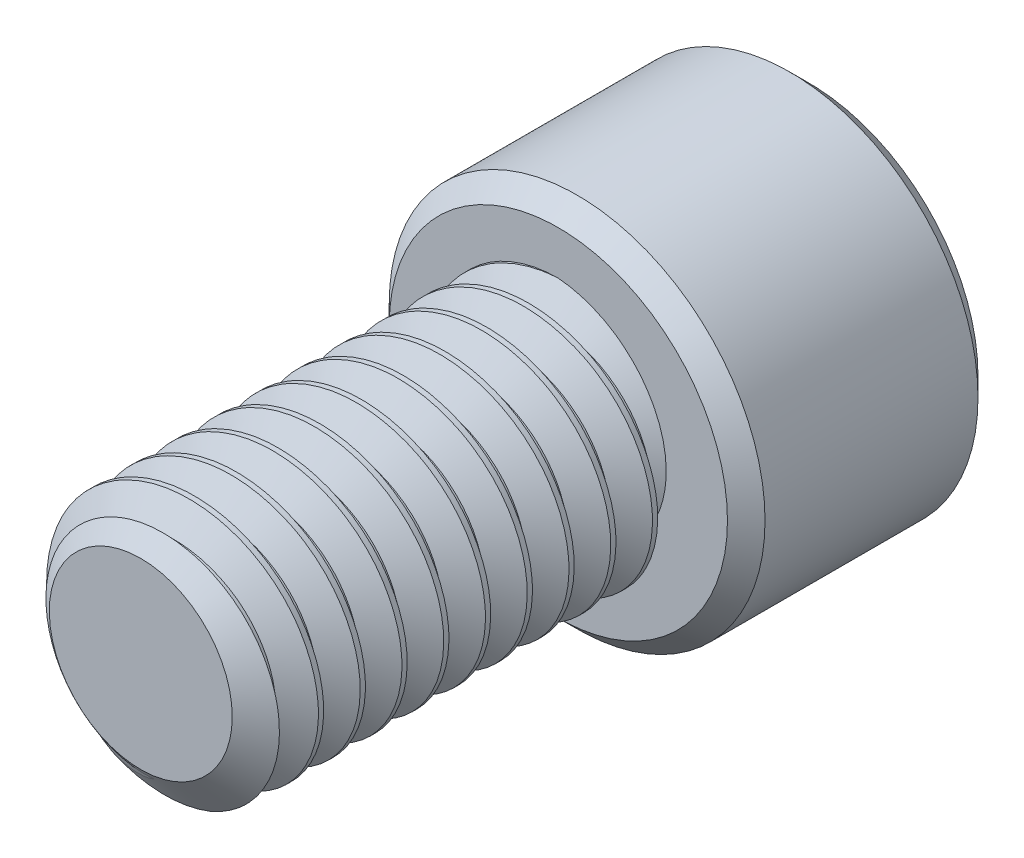
SolidWorks part; units mm, degrees
ref_plane "Front Plane" through (0, 0, 0) normal (0, 0, 1) x (1, 0, 0)
ref_plane "Top Plane" through (0, 0, 0) normal (0, 1, 0) x (1, 0, 0)
ref_plane "Right Plane" through (0, 0, 0) normal (1, 0, 0) x (0, 0, -1)
sketch "Sketch1" plane through (0, 0, 0) normal (0, 0, 1) x (1, 0, 0)
  circle A0 centre (0, 0) radius 4.7625
  dimension "OD" = 9.525
extrude "Extrude1" add sketch "Sketch1" against normal blind 15.875
sketch "Sketch2" plane through (0, 0, 0) normal (0, 0, 1) x (1, 0, 0)
  circle A0 centre (0, 0) radius 4.7625 construction
  circle A1 centre (0, 0) radius 4.7625
curve "Helix/Spiral1" pitch 1.5875 height 17.4625 turns 11 parameters "pitch"=1.5875
sketch "Sketch3" plane through (0, 0, 0) normal (1, 0, 0) x (0, 0, -1)
  line L0 (-1.3891, 4.7625) -> (-0.7938, 3.7314)
  line L1 (-0.7938, 3.7314) -> (-0.5953, 3.7314)
  line L2 (-0.5953, 3.7314) -> (0, 4.7625)
  line L3 (-1.3891, 4.7625) -> (0, 4.7625)
  line L4 (-0.6945, 4.7625) -> (-0.6945, 3.7314) construction
  line L5 (-1.0914, 4.2469) -> (-0.2977, 4.2469) construction
  line L6 (0, 4.7625) -> (0, -4.7625) construction
  dimension "D1" = 0.1984
  dimension "D2" = 0.7937
  dimension "D3" = 60
sweep "Cut-Sweep1" cut profiles "Sketch3" path "Helix/Spiral1"
sketch "Sketch4" plane through (0, 0, 0) normal (1, 0, 0) x (0, 0, -1)
  line L0 (0.8998, 4.7625) -> (0, 3.4774)
  line L1 (0, 3.4774) -> (0, 4.7625)
  line L2 (0.8998, 4.7625) -> (0, 4.7625)
  line L3 (-1.3891, 4.7625) -> (0, 4.7625) construction
  line L4 (0, 0) -> (7.0209, 0) construction
  dimension "D1" = 55
  dimension "D2" = 0.254
revolve "Cut-Revolve1" cut sketch "Sketch4" angle 360 about L4
sketch "Sketch5" plane through (0, 0, 0) normal (1, 0, 0) x (0, 0, -1)
  line L0 (15.875, -3.7535) -> (15.875, 3.3982) construction
  line L1 (15.875, 4.8895) -> (87.4665, 4.8895)
  line L2 (15.875, 4.8895) -> (15.875, 0)
  line L3 (15.875, 0) -> (87.3125, 0)
  line L4 (87.3125, 4.5593) -> (87.3125, 0)
  line L5 (87.4665, 4.8895) -> (87.3125, 4.5593)
  line L6 (0, 0) -> (9.9695, 0) construction
  point P3 (87.3125, 4.8895)
  point P10 (87.3125, 4.8895)
  dimension "D1" = 0.3302
  dimension "Thread min" = 87.3125
  dimension "D2" = 0.127
  dimension "D3" = 25
revolve "partially thread" add sketch "Sketch5" angle 360 about L6
sketch "Sketch6" plane through (0, 0, -15.875) normal (0, 0, -1) x (-1, 0, 0)
  circle A0 centre (0, 0) radius 7.1438
  dimension "head dia" = 14.2875
extrude "Extrude2" add sketch "Sketch6" along normal blind 9.525
sketch "Sketch7" plane through (0, 0, -25.4) normal (0, 0, -1) x (-1, 0, 0)
  line L1 (0, 4.5827) -> (-3.9688, 2.2914)
  line L2 (-3.9688, 2.2914) -> (-3.9688, -2.2914)
  line L3 (-3.9688, -2.2914) -> (0, -4.5827)
  line L4 (0, -4.5827) -> (3.9688, -2.2914)
  line L5 (3.9688, -2.2914) -> (3.9688, 2.2914)
  line L6 (3.9688, 2.2914) -> (0, 4.5827)
  circle A0 centre (0, 0) radius 3.9688 construction
  dimension "hex dia" = 7.9375
extrude "Cut-Extrude1" cut sketch "Sketch7" against normal blind 5.9531
sketch "Sketch8" plane through (0, 0, -25.4) normal (0, 0, -1) x (-1, 0, 0)
  circle A0 centre (0, 0) radius 4.5827
extrude "Cut-Extrude2" cut sketch "Sketch8" against normal through all draft 45
chamfer "Chamfer1" distance 0.7144 angle 45 2 edges at (-7.1438, 0, -25.4) (-7.1438, 0, -15.875)
sketch "Sketch9" plane through (0, 0, 0) normal (1, 0, 0) x (0, 0, -1)
  line L0 (0, 4.7625) -> (0, -4.7625) construction
  line L1 (8.7312, 4.7625) -> (8.7312, -4.7625) construction
  dimension "D1" = 8.7312
  dimension "D4" = 0.635
  dimension "D5" = 0.3302
equation "\"D3@Helix/Spiral1\" = \"screw length@Extrude1\"+\"pitch@Helix/Spiral1\""
equation "\"D1@Sketch3\" = \"pitch@Helix/Spiral1\"*.125"
equation "\"D2@Sketch3\" = \"pitch@Helix/Spiral1\"*.5"
equation "\"D1@Cut-Extrude1\" = \"hex dia@Sketch7\"*.75"
equation "\"D1@Chamfer1\" = \"head dia@Sketch6\"*.05"
equation "\"D1@Sketch9\" = \"pitch@Helix/Spiral1\"*5.5"
